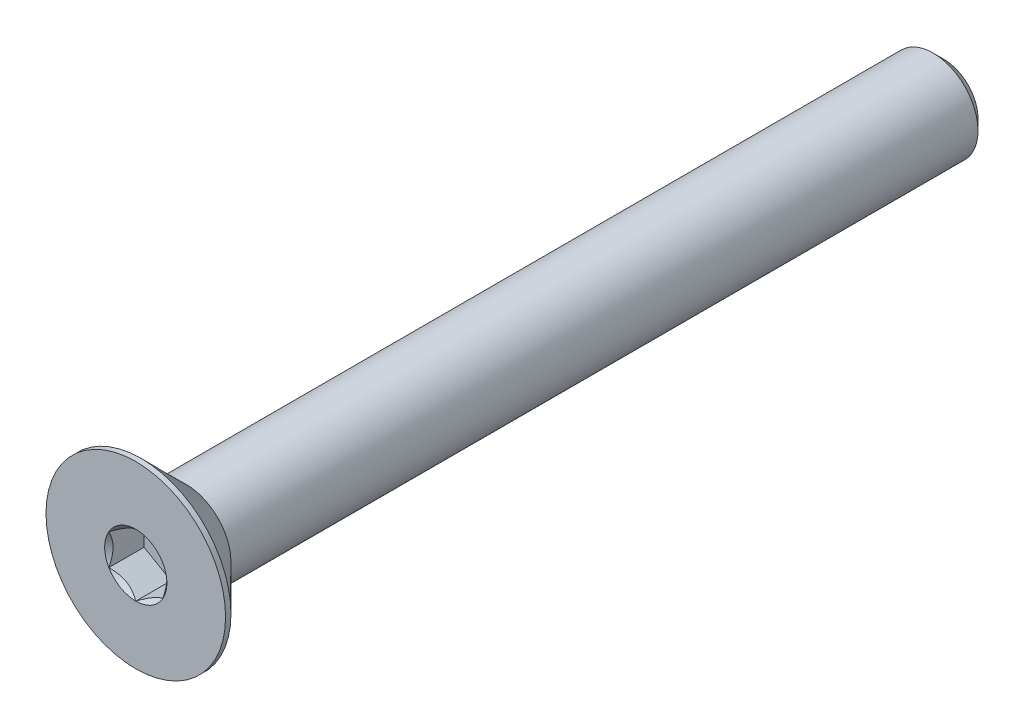
SolidWorks part; units mm, degrees
ref_plane "Front" through (0, 0, 0) normal (0, 0, 1) x (1, 0, 0)
ref_plane "Top" through (0, 0, 0) normal (0, 1, 0) x (1, 0, 0)
ref_plane "Right" through (0, 0, 0) normal (1, 0, 0) x (0, 0, -1)
sketch "Sketch1" plane through (0, 0, 0) normal (1, 0, 0) x (0, 0, -1)
  line L0 (0, 5) -> (0.3, 5) construction
  line L1 (0.3, 5) -> (2.8, 2.5) construction
  line L2 (0, 2.5) -> (45, 2.5)
  line L3 (45, 2.5) -> (45, 0)
  line L4 (45, 0) -> (0, 0)
  line L5 (0, 0) -> (0, 5) construction
  line L6 (0, 5) -> (0, -5) construction
  line L7 (45, 2.5) -> (45, -2.5) construction
  line L8 (0, -5) -> (0.3, -5) construction
  line L9 (0.3, -5) -> (2.8, -2.5) construction
  line L11 (0, 2.5) -> (0, 0)
  line L12 (2.8, 2.5) -> (2.8, 0) construction
  dimension "Head Ht" = 2.8
  dimension "Head Dia" = 10
  dimension "Dia" = 5
  dimension "Lg" = 45
  dimension "Head Angle" = 90
revolve "Revolve1" add sketch "Sketch1" angle 360 mid plane about L4
sketch "Sketch3" plane through (0, 0, -45) normal (0, 0, -1) x (-1, 0, 0)
  circle A0 centre (0, 0) radius 2.5
curve "Helix/Spiral1" pitch 0.8 height 45 turns 56.25
sketch "Sketch2" plane through (0, 0, 0) normal (1, 0, 0) x (0, 0, -1)
  line L0 (45, 2.5) -> (45.7, 2.5)
  line L1 (45.7, 2.5) -> (45.4, 1.9804)
  line L2 (45.4, 1.9804) -> (45.3, 1.9804)
  line L3 (45.3, 1.9804) -> (45, 2.5)
  line L4 (45.15, 2.2402) -> (45.55, 2.2402) construction
  dimension "D1" = 60
  dimension "D2" = 0.1
  dimension "D3" = 0.4
chamfer "Chamfer1" distance 0.6 angle 45 1 edges at (0, 2.5, -45)
sweep "Cut-Sweep1" [suppressed] cut profiles "Sketch2" path "Helix/Spiral1"
sketch "Sketch7" plane through (0, 0, 0) normal (1, 0, 0) x (0, 0, -1)
  line L0 (0, 5) -> (0.3, 5) construction
  line L1 (0.3, 5) -> (2.8, 2.5) construction
  line L2 (0, 5) -> (0.3, 5)
  line L3 (0.3, 5) -> (2.8, 2.5)
  line L4 (2.8, 2.5) -> (2.8, 0) construction
  line L5 (2.8, 2.5) -> (2.8, 0)
  line L7 (0, 0) -> (0, 5) construction
  line L8 (0, 0) -> (0, 5)
  line L9 (0, 0) -> (2.8, 0)
  line L10 (5.5, 0) -> (-5.5, 0) construction
revolve "Revolve2" add sketch "Sketch7" angle 360 mid plane about L9
ref_plane "Plane1" through (0, 0, -2.8) normal (0, 0, 1) x (1, 0, 0)
sketch "Sketch8" plane through (0, 0, -2.8) normal (0, 0, 1) x (1, 0, 0)
  circle A0 centre (0, 0) radius 2.5
extrude "Boss-Extrude1" add sketch "Sketch8" against normal through all draft 45
sketch "Sketch5" plane through (0, 0, 0) normal (0, 0, 1) x (1, 0, 0)
  line L1 (1.5, -0.866) -> (1.5, 0.866)
  line L2 (1.5, 0.866) -> (0, 1.7321)
  line L3 (0, 1.7321) -> (-1.5, 0.866)
  line L4 (-1.5, 0.866) -> (-1.5, -0.866)
  line L5 (-1.5, -0.866) -> (0, -1.7321)
  line L6 (0, -1.7321) -> (1.5, -0.866)
  circle A0 centre (0, 0) radius 1.5 construction
  dimension "Hex" = 3
extrude "Cut-Extrude2" cut sketch "Sketch5" against normal blind 1.96
sketch "Sketch6" plane through (0, 0, 0) normal (0, 0, 1) x (1, 0, 0)
  circle A0 centre (0, 0) radius 1.7321
extrude "Cut-Extrude3" cut sketch "Sketch6" against normal blind 1.96 draft 45
sketch "Sketch9" [suppressed] plane through (0, 0, -5.5) normal (0, 0, 1) x (1, 0, 0)
  circle A1 centre (0, 0) radius 5
  circle A2 centre (0, 0) radius 5
  point P0 (0, 5)
  dimension "D1" = 0
extrude "Boss-Extrude2" [suppressed] add sketch "Sketch9" against normal offset from surface (18.5 mm away) 26
fillet "Fillet1" [suppressed] radius 0.5
sketch "Sketch10" plane through (0, 0, 0) normal (1, 0, 0) x (0, 0, -1)
  line L0 (45, 2.5) -> (45, -2.5) construction
  point P0 (43.8, -2.5)
  dimension "D1" = 1.2
equation "\"D3@Helix/Spiral1\" = \"Lg@Sketch1\""
equation "\"D2@Sketch2\" = \"D4@Helix/Spiral1\" * .125"
equation "\"D3@Sketch2\" = \"D4@Helix/Spiral1\" * .5"
equation "\"D1@Chamfer1\" = \"D4@Helix/Spiral1\" * .75"
equation "\"D1@Cut-Extrude2\" = \"Head Ht@Sketch1\" * .7"
equation "\"D1@Sketch10\" = \"D4@Helix/Spiral1\" * 1.5"
equation "\"D1@Cut-Extrude3\" = \"D1@Cut-Extrude2\""
equation "\"D1@Fillet1\" = \"Dia@Sketch1\" * .1"
